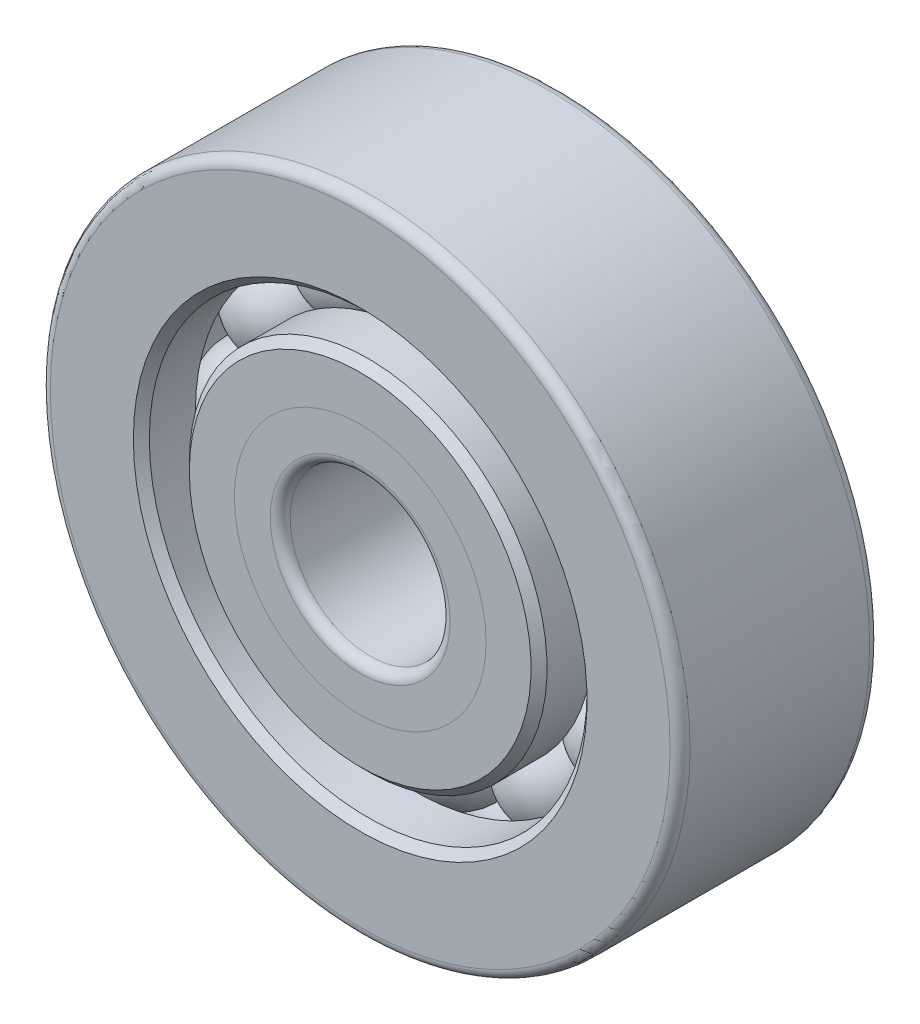
SolidWorks part; units mm, degrees
ref_plane "Front Plane" through (0, 0, 0) normal (0, 0, 1) x (1, 0, 0)
ref_plane "Top Plane" through (0, 0, 0) normal (0, 1, 0) x (1, 0, 0)
ref_plane "Right Plane" through (0, 0, 0) normal (1, 0, 0) x (0, 0, -1)
sketch "Sketch1" plane through (0, 0, 0) normal (1, 0, 0) x (0, 0, -1)
  line L0 (-3.9624, 0) -> (3.9624, 0) construction
  line L9 (0, 12.7) -> (0, 0) construction
  line L10 (-3.9624, 3.175) -> (3.9624, 3.175)
  line L11 (3.9624, 3.175) -> (3.9624, 7.1016)
  line L12 (3.9624, 7.1016) -> (-3.9624, 7.1016)
  line L13 (-3.9624, 7.1016) -> (-3.9624, 3.175)
  line L14 (-3.9624, 8.6896) -> (3.9624, 8.6896)
  line L15 (3.9624, 8.6896) -> (3.9624, 12.7)
  line L16 (3.9624, 12.7) -> (-3.9624, 12.7)
  line L17 (-3.9624, 12.7) -> (-3.9624, 8.6896)
  line L18 (-1.985, 7.8956) -> (1.985, 7.8956) construction
  line L20 (3.9624, 4.9987) -> (-3.9624, 4.9987) construction
  line L21 (0, 5.9106) -> (0, 4.9987)
  line L22 (0, 4.9987) -> (0, 4.0869)
  line L23 (0, 4.0869) -> (0, 3.175)
  circle A0 centre (0, 7.8956) radius 1.985
  point P17 (0, 9.8806)
  dimension "ID" = 6.35
  dimension "OD" = 25.4
  dimension "Ball Diameter" = 3.97
  dimension "Ball Pattern Diameter" = 15.7912
  dimension "D6" = 1.588
  dimension "Width" = 7.9248
sketch "Sketch2" plane through (0, 0, 0) normal (0, 0, 1) x (1, 0, 0)
  circle A0 centre (0, 0) radius 7.8956 construction
  circle A1 centre (0, 7.8956) radius 1.985
  circle A2 centre (3.9478, 6.8378) radius 1.985
  circle A3 centre (6.8378, 3.9478) radius 1.985
  circle A4 centre (7.8956, 0) radius 1.985
  circle A5 centre (6.8378, -3.9478) radius 1.985
  circle A6 centre (3.9478, -6.8378) radius 1.985
  circle A7 centre (0, -7.8956) radius 1.985
  circle A8 centre (-3.9478, -6.8378) radius 1.985
  circle A9 centre (-6.8378, -3.9478) radius 1.985
  circle A10 centre (-7.8956, 0) radius 1.985
  circle A11 centre (-6.8378, 3.9478) radius 1.985
  circle A12 centre (-3.9478, 6.8378) radius 1.985
  circle A15 centre (0, 0) radius 3.175 construction
  circle A16 centre (0, 0) radius 12.7 construction
  point P36 (0, 0)
  dimension "ID" = 6.35
  dimension "OD" = 25.4
  dimension "No. of Balls" = 12
sketch "Sketch3" plane through (0, 0, 0) normal (1, 0, 0) x (0, 0, -1)
  line L1 (3.9624, 3.175) -> (3.9624, 7.1016) construction
  line L2 (-3.9624, 7.1016) -> (-3.9624, 3.175) construction
  line L3 (3.9624, 7.1016) -> (-3.9624, 7.1016) construction
  line L5 (3.9624, 3.175) -> (3.9624, 7.1016)
  line L6 (-3.9624, 7.1016) -> (-3.9624, 3.175)
  line L7 (3.9624, 7.1016) -> (-3.9624, 7.1016)
  line L8 (-3.9624, 12.7) -> (-3.9624, 8.6896) construction
  line L9 (3.9624, 12.7) -> (-3.9624, 12.7) construction
  line L10 (3.9624, 8.6896) -> (3.9624, 12.7) construction
  line L11 (-3.9624, 8.6896) -> (3.9624, 8.6896) construction
  line L12 (-3.9624, 12.7) -> (-3.9624, 8.6896)
  line L13 (3.9624, 12.7) -> (-3.9624, 12.7)
  line L14 (3.9624, 8.6896) -> (3.9624, 12.7)
  line L15 (-3.9624, 8.6896) -> (3.9624, 8.6896)
  line L16 (-3.9624, 3.175) -> (3.9624, 3.175) construction
  line L17 (-3.9624, 3.175) -> (3.9624, 3.175)
revolve "Revolve2" add sketch "Sketch3" angle 360 about L0
sketch "Sketch4" plane through (0, 0, 0) normal (1, 0, 0) x (0, 0, -1)
  circle A0 centre (0, 7.8956) radius 1.985 construction
  circle A1 centre (0, 7.8956) radius 1.985
revolve "Cut-Revolve1" cut sketch "Sketch4" angle 360 about L0
sketch "Sketch5" plane through (0, 0, 0) normal (1, 0, 0) x (0, 0, -1)
  line L0 (-1.985, 7.8956) -> (1.985, 7.8956) construction
  line L1 (-1.985, 7.8956) -> (1.985, 7.8956)
  circle A0 centre (0, 7.8956) radius 1.985 construction
  arc A1 (1.985, 7.8956) -> (-1.985, 7.8956) centre (0, 7.8956) ccw
revolve "Revolve3" add sketch "Sketch5" angle 360 about L18
pattern_circular "CirPattern1" count 12 over 360 about axis through (0, 0, 3.9624) along (0, 0, -1) of bodies 109
fillet "Fillet1" radius 0.3962 2 edges at (12.7, 0, 3.9624) (12.7, 0, -3.9624)
fillet "Fillet2" radius 0.3962 2 edges at (3.175, 0, -3.9624) (3.175, 0, 3.9624)
chamfer "Chamfer1" distance 0.317 angle 45 2 edges at (8.6896, 0, -3.9624) (8.6896, 0, 3.9624)
chamfer "Chamfer2" distance 0.317 angle 45 2 edges at (7.1016, 0, 3.9624) (7.1016, 0, -3.9624)
sketch "Split Line" plane through (0, 0, 0) normal (0, 0, 1) x (1, 0, 0)
  circle A0 centre (0, 0) radius 4.9987
split "Split1" trim tools "Split Line" bodies to split 108 resulting bodies 128 129
equation "\"D1@CirPattern1\"=\"No. of Balls@Sketch2\""
equation "\"D6@Sketch1\"=\"Ball Diameter@Sketch1\"*0.4"
equation "\"D1@Fillet1\"=\"Width@Sketch1\"/20"
equation "\"D1@Fillet2\"=\"Width@Sketch1\"/20"
equation "\"D1@Chamfer1\"=\"Width@Sketch1\"/25"
equation "\"D1@Chamfer2\"=\"Width@Sketch1\"/25"
equation "\"ID@Sketch2\"=\"ID@Sketch1\""
equation "\"OD@Sketch2\" = \"OD@Sketch1\""
